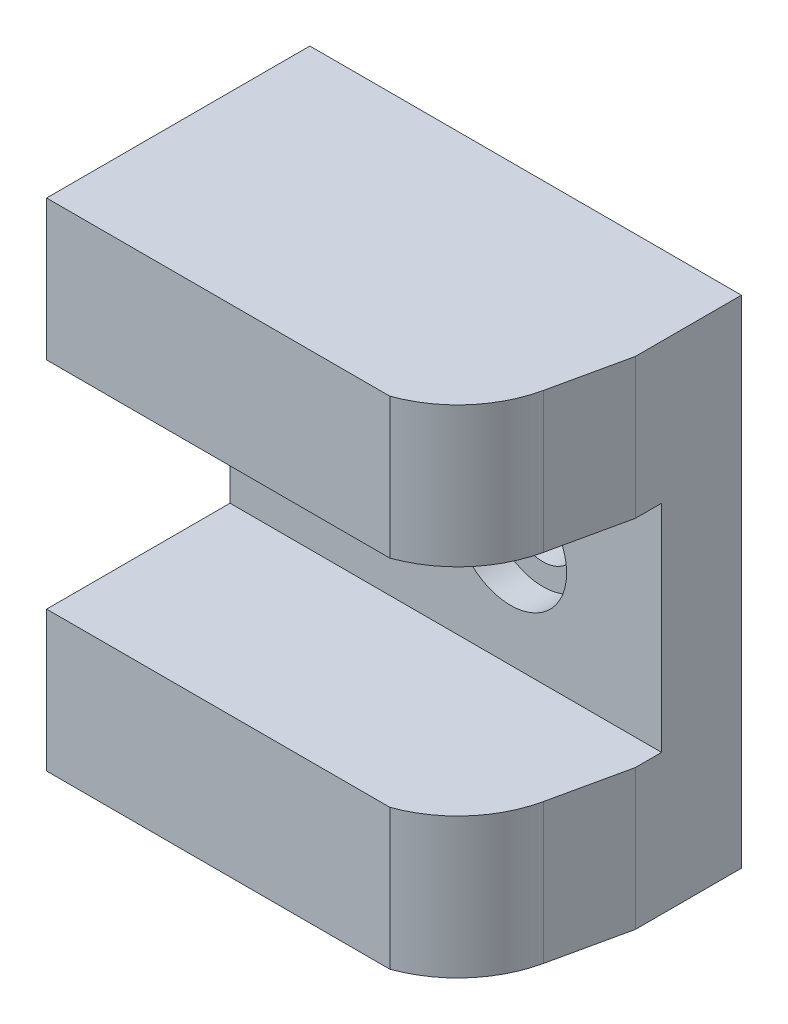
SolidWorks part; units mm, degrees
ref_plane "前视基准面" through (0, 0, 0) normal (0, 0, 1) x (1, 0, 0)
ref_plane "上视基准面" through (0, 0, 0) normal (0, 1, 0) x (1, 0, 0)
ref_plane "右视基准面" through (0, 0, 0) normal (1, 0, 0) x (0, 0, -1)
sketch "草图1" plane through (0, 0, 0) normal (0, 0, 1) x (1, 0, 0)
  line L0 (130, 105) -> (130, -105) construction
  line L1 (130, 82) -> (110, 82)
  line L2 (130, 82) -> (130, 105)
  line L4 (110, 82) -> (110, 105)
  line L5 (75, 105) -> (130, 105) construction
  line L6 (130, 105) -> (110, 105)
  dimension "D1" = 20
  dimension "D2" = 23
extrude "凸台-拉伸1" add sketch "草图1" along normal blind 12.2
sketch "草图2" plane through (0, 105, 0) normal (0, 1, 0) x (1, 0, 0)
  line L0 (130, -12.2) -> (130, 0) construction
  line L6 (129.2354, -8.4138) -> (130, -4.9174)
  line L8 (130, -4.9174) -> (130, -12.4992)
  line L10 (130, -12.4992) -> (124.3532, -12.4992)
  arc A1 (124.3532, -12.4992) -> (129.2354, -8.4138) centre (124.1554, -7.3029) ccw
extrude "切除-拉伸1" cut sketch "草图2" against normal blind 26.5
sketch "草图3" plane through (0, 0, 12.2) normal (0, 0, 1) x (1, 0, 0)
  line L0 (110, 93.5) -> (130, 93.5) construction
  line L1 (110, 105) -> (110, 82) construction
  line L4 (110, 98.5) -> (130, 98.5)
  line L5 (110, 98.5) -> (110, 88.5)
  line L6 (110, 88.5) -> (130, 88.5)
  line L7 (130, 98.5) -> (130, 88.5)
  line L8 (110, 98.5) -> (130, 88.5) construction
  line L9 (110, 88.5) -> (130, 98.5) construction
  point P6 (120, 93.5)
  dimension "D1" = 10
  dimension "D2" = 20
extrude "切除-拉伸2" cut sketch "草图3" against normal blind 8.5
sketch "草图4" plane through (0, 0, 3.7) normal (0, 0, 1) x (1, 0, 0)
  line L0 (110, 93.5) -> (130, 93.5) construction
  line L1 (110, 98.5) -> (110, 88.5) construction
  line L3 (130, 88.5) -> (130, 98.5) construction
  circle A0 centre (115, 93.5) radius 1.5
  circle A2 centre (123, 93.5) radius 1.5
  dimension "D1" = 3
  dimension "D2" = 8
  dimension "D3" = 5
hole_wizard "M3 六角头螺栓的柱形沉头孔1" positions "草图7" profile "草图8" counterbore size "M3" standard "GB" end condition through all
sketch "草图7" plane through (0, 0, 3.7) normal (0, 0, 1) x (1, 0, 0)
  point P0 (115, 93.5)
  point P3 (123, 93.5)
sketch "草图8" plane through (115, 93.5, 3.7) normal (1, 0, 0) x (0, -1, 0)
  line L0 (0, 0) -> (0, 3.7)
  line L1 (0, 3.7) -> (1.6, 3.7)
  line L3 (1.6, 3.7) -> (1.6, 1.5)
  line L4 (1.6, 1.5) -> (2.6, 1.5)
  line L5 (2.6, 1.5) -> (2.6, 0)
  line L7 (2.6, 0) -> (0, 0)
  line L11 (0, -6.35) -> (0, 107.95) construction
  dimension "通孔孔直径" = 3.2
  dimension "通孔孔深度" = 3.7
  dimension "柱形沉头孔直径" = 5.2
  dimension "柱形沉头孔深度" = 1.5
move or copy body "实体-移动/复制1" [suppressed] bodies to move or copy 109
